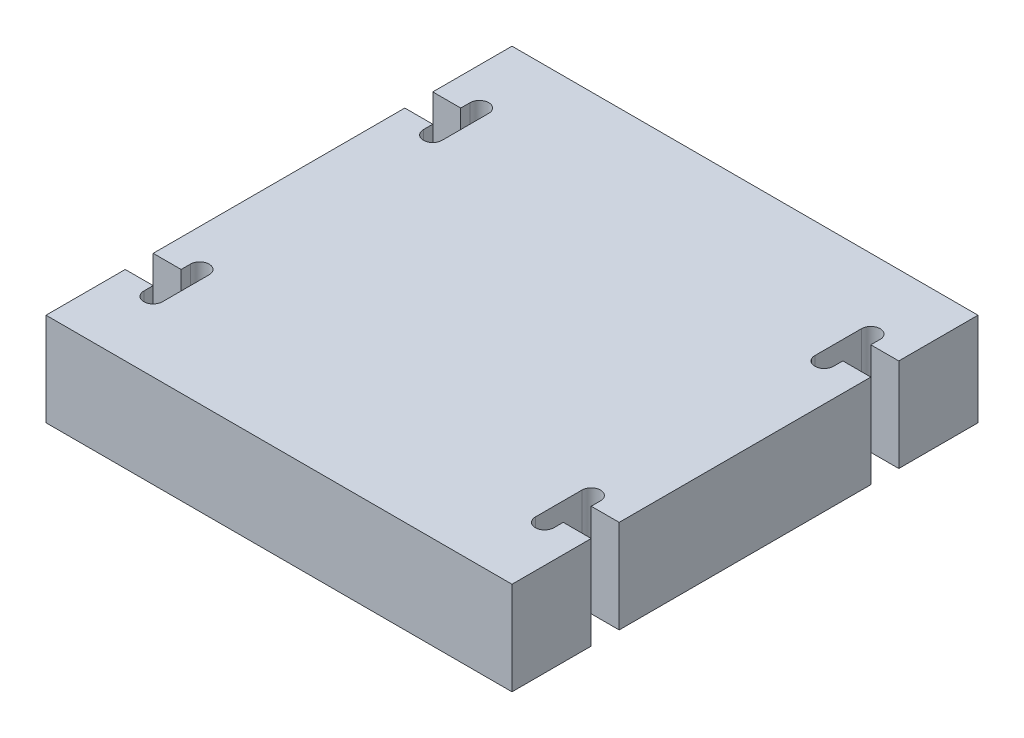
SolidWorks part; units mm, degrees
ref_plane "Front Plane" through (0, 0, 0) normal (0, 0, 1) x (1, 0, 0)
ref_plane "Top Plane" through (0, 0, 0) normal (0, 1, 0) x (1, 0, 0)
ref_plane "Right Plane" through (0, 0, 0) normal (1, 0, 0) x (0, 0, -1)
sketch "Sketch1" plane through (0, 0, 0) normal (0, 1, 0) x (1, 0, 0)
  line L1 (-25, -25) -> (25, -25)
  line L2 (-25, -25) -> (-25, 25)
  line L3 (-25, 25) -> (25, 25)
  line L4 (25, -25) -> (25, 25)
  line L5 (-25, -25) -> (25, 25) construction
  line L6 (-25, 25) -> (25, -25) construction
  point P0 (0, 0)
  dimension "D1" = 50
  dimension "D2" = 50
extrude "Boss-Extrude1" add sketch "Sketch1" along normal blind 5 and the other way blind 5
sketch "Sketch2" plane through (0, 5, 0) normal (0, 1, 0) x (-1, 0, 0)
  line L0 (25, -15) -> (22, -15) construction
  line L1 (25, -25) -> (25, 25) construction
  line L2 (25, 15) -> (22, 15) construction
  line L3 (25, -13.5) -> (22, -13.5)
  line L4 (25, -16.5) -> (22, -16.5)
  line L5 (25, 16.5) -> (22, 16.5)
  line L6 (25, 13.5) -> (22, 13.5)
  line L7 (25, -13.5) -> (25, 13.5) construction
  line L8 (21, -17.5) -> (21, -12.5) construction
  line L9 (20, -17.5) -> (20, -12.5)
  line L10 (22, -17.5) -> (22, -16.5)
  line L11 (22, -13.5) -> (22, -12.5)
  line L12 (20, -13.5) -> (20, -12.5)
  line L13 (20, -17.5) -> (20, -16.5)
  line L14 (22, -17.5) -> (22, -12.5)
  line L15 (25, 0) -> (0, 0) construction
  line L16 (21, 17.5) -> (21, 12.5) construction
  line L17 (22, 17.5) -> (22, 12.5)
  line L18 (20, 17.5) -> (20, 16.5)
  line L19 (20, 13.5) -> (20, 12.5)
  line L20 (22, 13.5) -> (22, 12.5)
  line L21 (22, 17.5) -> (22, 16.5)
  line L22 (20, 17.5) -> (20, 12.5)
  arc A0 (20, -17.5) -> (22, -17.5) centre (21, -17.5) ccw
  arc A1 (22, -12.5) -> (20, -12.5) centre (21, -12.5) ccw
  arc A2 (22, 12.5) -> (20, 12.5) centre (21, 12.5) cw
  arc A3 (20, 17.5) -> (22, 17.5) centre (21, 17.5) cw
  point P14 (25, 0)
  point P17 (21, -15)
  point P35 (21, 15)
  line M3 (25, -25) -> (25, 25)
  dimension "D6" = 3
  dimension "D7" = 2
  dimension "D8" = 5
  dimension "D3" = 30
  dimension "D1" = 1.5
  dimension "D2" = 1.5
  dimension "D4" = 1.5
extrude "Cut-Extrude1" cut sketch "Sketch2" against normal blind 10 contours L11 A1 L9 A0 L10 L14 | L14 L4 L3 M3 | L5 L17 L6 M3 | A3 L18 L22 L19 A2 L17 region at (-23.5, 5, -15) region at (-23.5, 5, 15) region at (-21, 5, -15) region at (-21, 5, 15)
mirror "Mirror1" about plane through (0, 0, 0) normal (1, 0, 0) of "Cut-Extrude1"
